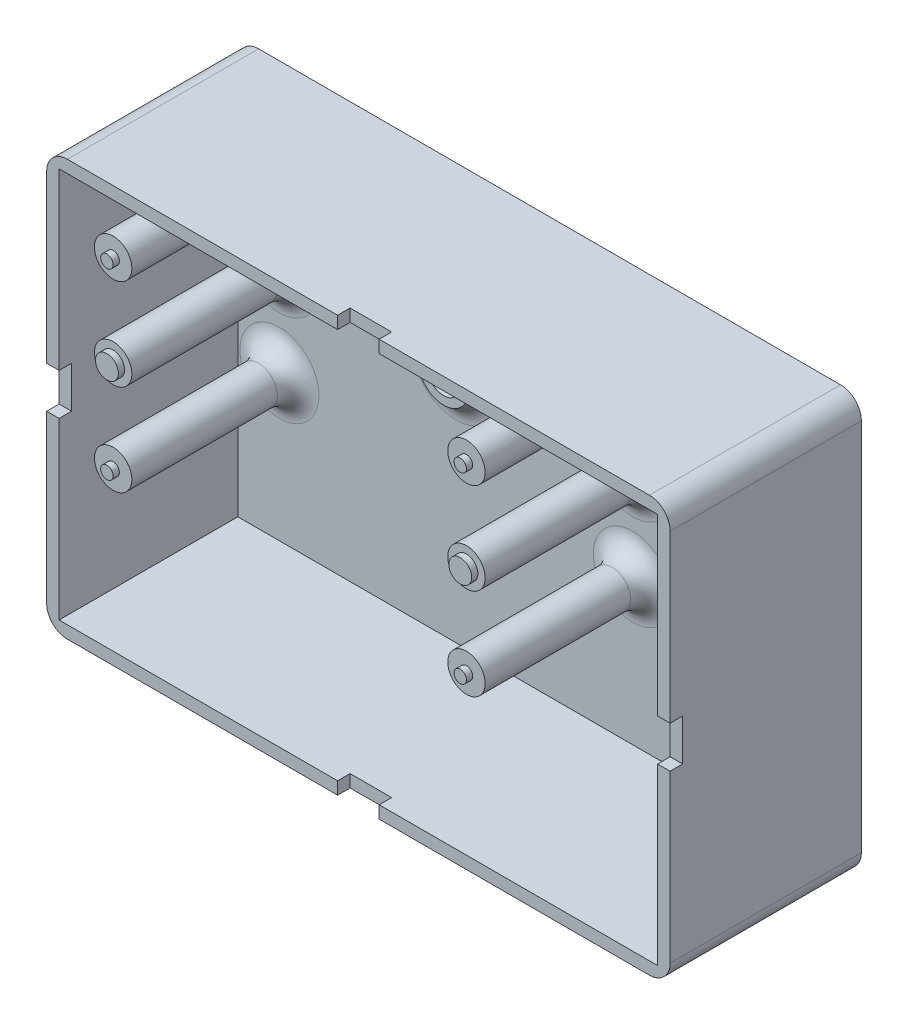
SolidWorks part; units mm, degrees
ref_plane "前视基准面" through (0, 0, 0) normal (0, 0, 1) x (1, 0, 0)
ref_plane "上视基准面" through (0, 0, 0) normal (0, 1, 0) x (1, 0, 0)
ref_plane "右视基准面" through (0, 0, 0) normal (1, 0, 0) x (0, 0, -1)
sketch "草图1" plane through (0, 0, 0) normal (0, 0, 1) x (1, 0, 0)
  line L1 (-75, -50) -> (75, -50)
  line L2 (-75, -50) -> (-75, 50)
  line L3 (-75, 50) -> (75, 50)
  line L4 (75, -50) -> (75, 50)
  line L5 (-75, -50) -> (75, 50) construction
  line L6 (-75, 50) -> (75, -50) construction
  line L7 (-72, 47) -> (72, 47)
  line L8 (-72, 47) -> (-72, -47)
  line L9 (-72, -47) -> (72, -47)
  line L10 (72, 47) -> (72, -47)
  line L11 (-72, 47) -> (72, -47) construction
  line L12 (-72, -47) -> (72, 47) construction
  point P0 (0, 0)
  point P6 (0, 0)
  dimension "D1" = 150
  dimension "D2" = 100
  dimension "D3" = 144
  dimension "D4" = 94
extrude "凸台-拉伸1" add sketch "草图1" along normal blind 46 contours L3 L4 L1 L2
sketch "草图3" plane through (0, 0, 46) normal (0, 0, 1) x (1, 0, 0)
  line L1 (-72, 47) -> (72, 47)
  line L2 (-72, 47) -> (-72, -47)
  line L3 (-72, -47) -> (72, -47)
  line L4 (72, 47) -> (72, -47)
  line L5 (-72, 47) -> (72, -47) construction
  line L6 (-72, -47) -> (72, 47) construction
  point P0 (0, 0)
  dimension "D1" = 144
  dimension "D2" = 94
extrude "切除-拉伸2" cut sketch "草图3" against normal blind 43
sketch "草图5" plane through (0, 0, 3) normal (0, 0, 1) x (1, 0, 0)
  line L0 (72, 47) -> (-72, 47) construction
  line L1 (72, 47) -> (-72, 47) construction
  line L2 (-72, 47) -> (-72, -47) construction
  line L3 (-72, 47) -> (-72, -47) construction
  circle A0 centre (-62, 32) radius 4.5
  circle A1 centre (23, 32) radius 4.5
  circle A2 centre (-62, -12) radius 4.5
  circle A3 centre (23, -12) radius 4.5
  circle A4 centre (23, 10) radius 4.5
  circle A5 centre (-62, 10) radius 4.5
  dimension "D1" = 9
  dimension "D2" = 9
  dimension "D3" = 9
  dimension "D4" = 9
  dimension "D5" = 9
  dimension "D6" = 9
  dimension "D7" = 85
  dimension "D8" = 85
  dimension "D9" = 85
  dimension "D10" = 15
  dimension "D11" = 22
  dimension "D12" = 10
  dimension "D13" = 10
  dimension "D14" = 10
  dimension "D15" = 15
  dimension "D16" = 22
  dimension "D17" = 22
  dimension "D18" = 22
extrude "凸台-拉伸3" add sketch "草图5" along normal blind 40
sketch "草图6" plane through (0, 0, 3) normal (0, 0, 1) x (1, 0, 0)
  circle A0 centre (-19.5, 10) radius 6
  circle A1 centre (-19.5, 10) radius 4
  circle A2 centre (-62, 10) radius 3 construction
  circle A5 centre (23, 10) radius 3 construction
  circle A8 centre (-62, 10) radius 4.5 construction
  circle A9 centre (-62, 32) radius 4.5 construction
  point P7 (-13.0554, 17.503)
  dimension "D3" = 12
  dimension "D4" = 42.5
  dimension "D5" = 22
  dimension "D2" = 8
  dimension "D1" = 85
extrude "凸台-拉伸4" add sketch "草图6" along normal blind 3
sketch "草图7" plane through (0, 0, 43) normal (0, 0, 1) x (1, 0, 0)
  circle A0 centre (-62, 32) radius 1.5
  circle A1 centre (23, 32) radius 1.5
  circle A2 centre (-62, 10) radius 2.75
  circle A3 centre (23, 10) radius 2.75
  circle A4 centre (23, -12) radius 1.5
  circle A5 centre (-62, -12) radius 1.5
  dimension "D1" = 3
  dimension "D2" = 3
  dimension "D3" = 3
  dimension "D4" = 3
  dimension "D5" = 5.5
  dimension "D6" = 5.5
extrude "凸台-拉伸5" add sketch "草图7" along normal blind 1.5
sketch "草图9" plane through (0, 0, 46) normal (0, 0, 1) x (1, 0, 0)
  line L0 (72, 47) -> (-72, 47) construction
  line L1 (-5, 44) -> (5, 44)
  line L2 (-5, 44) -> (-5, 50)
  line L3 (-5, 50) -> (5, 50)
  line L4 (5, 44) -> (5, 50)
  line L5 (-5, 44) -> (5, 50) construction
  line L6 (-5, 50) -> (5, 44) construction
  line L7 (-75, 50) -> (75, 50) construction
  line L8 (-75, -50) -> (75, -50) construction
  line L9 (-5, -53) -> (5, -53)
  line L10 (-5, -53) -> (-5, -47)
  line L11 (-5, -47) -> (5, -47)
  line L12 (5, -53) -> (5, -47)
  line L13 (-5, -53) -> (5, -47) construction
  line L14 (-5, -47) -> (5, -53) construction
  line L15 (-72, -47) -> (72, -47) construction
  line L16 (72, -47) -> (72, 47) construction
  line L17 (69, -5) -> (75, -5)
  line L18 (69, -5) -> (69, 5)
  line L19 (69, 5) -> (75, 5)
  line L20 (75, -5) -> (75, 5)
  line L21 (69, -5) -> (75, 5) construction
  line L22 (69, 5) -> (75, -5) construction
  line L23 (75, -50) -> (75, 50) construction
  line L24 (-72, 47) -> (-72, -47) construction
  line L25 (-69, -5) -> (-75, -5)
  line L26 (-69, -5) -> (-69, 5)
  line L27 (-69, 5) -> (-75, 5)
  line L28 (-75, -5) -> (-75, 5)
  line L29 (-69, -5) -> (-75, 5) construction
  line L30 (-69, 5) -> (-75, -5) construction
  line L31 (-75, -50) -> (-75, 50) construction
  point P0 (0, 47)
  point P9 (0, -50)
  point P18 (72, 0)
  point P27 (-72, 0)
  dimension "D1" = 10
  dimension "D2" = 10
  dimension "D3" = 10
  dimension "D4" = 10
extrude "切除-拉伸3" cut sketch "草图9" against normal blind 3
fillet "圆角1" radius 5 11 edges at (-57.5, 32, 3) (-75, -50, 23) (75, -50, 23) (75, 50, 23) (-75, 50, 23) (-13.5, 10, 3) (27.5, -12, 3) (-57.5, -12, 3) (-57.5, 10, 3) (27.5, 10, 3) (27.5, 32, 3)
